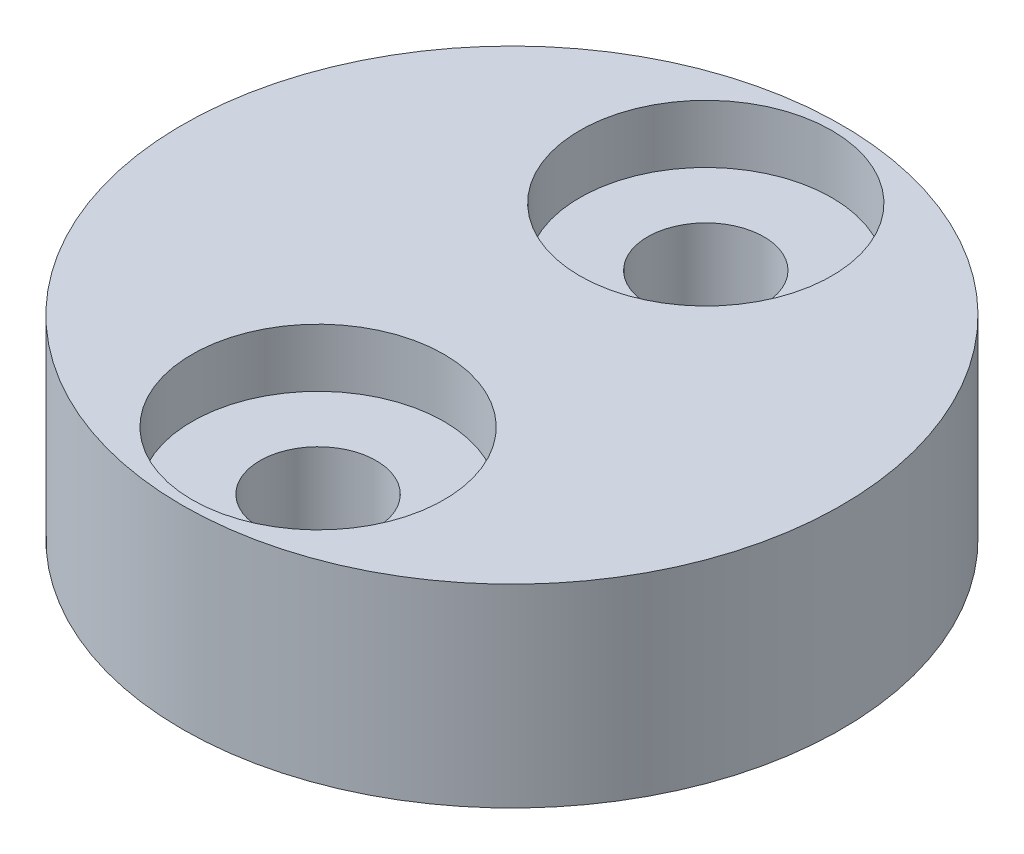
SolidWorks part; units mm, degrees
ref_plane "Front Plane" through (0, 0, 0) normal (0, 0, 1) x (1, 0, 0)
ref_plane "Top Plane" through (0, 0, 0) normal (0, 1, 0) x (1, 0, 0)
ref_plane "Right Plane" through (0, 0, 0) normal (1, 0, 0) x (0, 0, -1)
sketch "Sketch1" plane through (0, 0, 0) normal (0, 1, 0) x (1, 0, 0)
  circle A0 centre (0, 0) radius 8.5
  circle A1 centre (0, 0) radius 5 construction
  circle A3 centre (0, 5) radius 1.5
  circle A4 centre (0, -5) radius 1.5
  dimension "D1" = 17
  dimension "D2" = 10
  dimension "D3" = 3
extrude "Boss-Extrude1" add sketch "Sketch1" along normal blind 5
sketch "Sketch2" plane through (0, 5, 0) normal (0, 1, 0) x (1, 0, 0)
  circle A2 centre (0, 0) radius 5 construction
  circle A3 centre (0, 5) radius 3.25
  circle A4 centre (0, -5) radius 3.25
  point P12 (0, 0)
  dimension "D1" = 10
  dimension "D2" = 6.5
  dimension "D3" = 2
extrude "Cut-Extrude1" cut sketch "Sketch2" against normal blind 1.5
